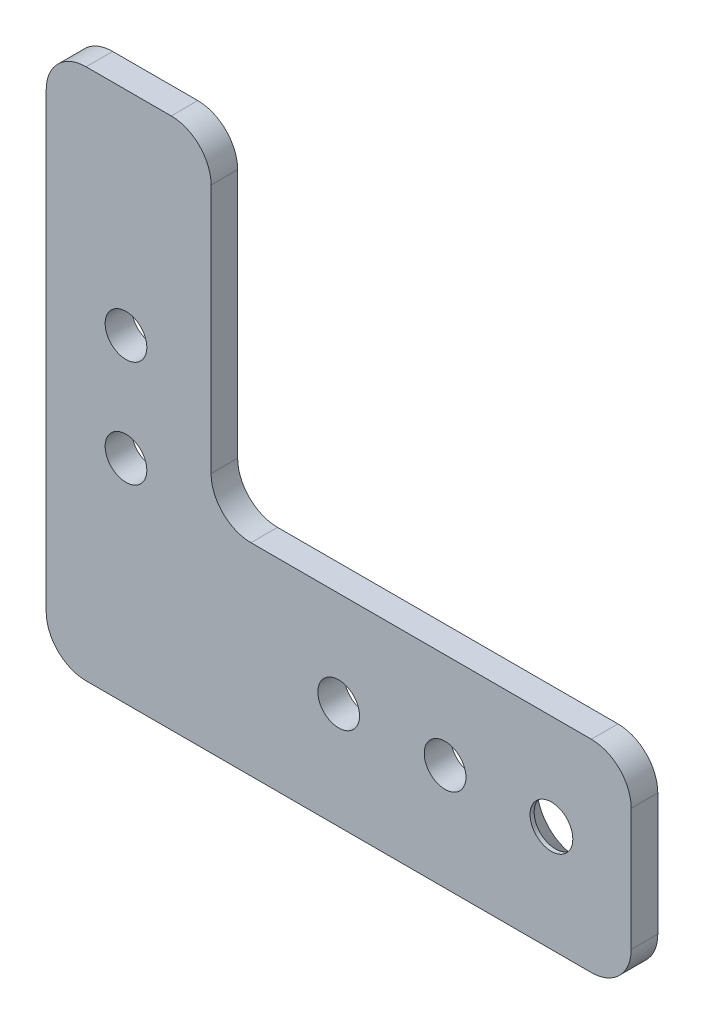
SolidWorks part; units mm, degrees
material "6061-T6 (SS)"
ref_plane "Front Plane" through (0, 0, 0) normal (0, 0, 1) x (1, 0, 0)
ref_plane "Top Plane" through (0, 0, 0) normal (0, 1, 0) x (1, 0, 0)
ref_plane "Right Plane" through (0, 0, 0) normal (1, 0, 0) x (0, 0, -1)
sketch "Sketch1" plane through (0, 0, 0) normal (0, 0, 1) x (1, 0, 0)
  line L0 (-15.24, 31.75) -> (-34.925, 31.75)
  line L1 (-34.925, -31.75) -> (34.925, -31.75) construction
  line L2 (-34.925, -31.75) -> (-34.925, 31.75)
  line L3 (-34.925, 31.75) -> (34.925, 31.75) construction
  line L4 (34.925, -31.75) -> (34.925, 31.75) construction
  line L5 (-34.925, -31.75) -> (34.925, 31.75) construction
  line L6 (-34.925, 31.75) -> (34.925, -31.75) construction
  line L7 (34.925, 31.75) -> (-15.24, 31.75) construction
  line L8 (34.925, 31.75) -> (34.925, -7.62) construction
  line L9 (34.925, -7.62) -> (-15.24, -7.62)
  line L10 (-15.24, 31.75) -> (-15.24, -7.62)
  line L19 (-25.4, 31.75) -> (-25.4, -31.75) construction
  line L20 (34.925, -7.62) -> (34.925, -31.75)
  line L24 (-34.925, -31.75) -> (34.925, -31.75)
  circle A0 centre (-25.4, -19.05) radius 2.4892
  circle A1 centre (-25.4, -6.35) radius 2.4892
  circle A2 centre (-25.4, 6.35) radius 2.4892
  circle A4 centre (0, -19.05) radius 2.4892
  circle A5 centre (12.7, -19.05) radius 2.4892
  circle A6 centre (25.4, -19.05) radius 2.4892
  point P0 (0, 0)
  dimension "D7" = 4.9784
  dimension "D1" = 69.85
  dimension "D2" = 63.5
  dimension "D3" = 24.13
  dimension "D4" = 19.685
  dimension "D5" = 9.525
  dimension "D6" = 34.925
  dimension "D9" = 12.7
  dimension "D10" = 12.7
  dimension "D11" = 12.7
  dimension "D13" = 12.7
  dimension "D15" = 12.7
base flange "Base-Flange1" sketch "Sketch1" thickness 3.175 reverse thickness direction no parameters "D1"=0.762
fillet "Fillet2" radius 4.7625 6 edges at (34.925, -31.75, -1.5875) (34.925, -7.62, -1.5875) (-15.24, -7.62, -1.5875) (-34.925, 31.75, -1.5875) (-34.925, -31.75, -1.5875) (-15.24, 31.75, -1.5875)
hole_wizard "CSK for #10 Flat Head Machine Screw1" positions "Sketch2" profile "Sketch3" countersink size "#10" standard "ANSI Inch"
sketch "Sketch2" plane through (0, 0, -3.175) normal (0, 0, -1) x (-1, 0, 0)
  point P0 (-25.4, -19.05)
  point P12 (0, 0)
  point P13 (0, -19.05)
  point P14 (0, 0)
  point P15 (-23.0546, -23.5031)
  point P16 (-25.4, -19.05)
  point P18 (0, 0)
sketch "Sketch3" plane through (25.4, -19.05, -3.175) normal (1, 0, 0) x (0, 1, 0)
  line L0 (0, 0) -> (0, 20.5838)
  line L1 (0, 20.5838) -> (2.5527, 19.05)
  line L2 (2.5527, 19.05) -> (2.5527, 2.6882)
  line L3 (2.5527, 2.6882) -> (4.8895, 0)
  line L5 (4.8895, 0) -> (0, 0)
  line L6 (-2.5527, 2.6882) -> (-4.8895, 0) construction
  line L10 (0, 20.5838) -> (-2.5527, 19.05) construction
  line L11 (0, -6.35) -> (0, 107.95) construction
  dimension "Hole Dia." = 5.1054
  dimension "Hole Depth" = 19.05
  dimension "Near C'Sink Dia." = 9.779
  dimension "Near C'Sink Angle" = 82
  dimension "Drill Angle" = 118
sketch "Bend-Lines1" [suppressed] plane through (0, 0, 0) normal (0, 1, 0) x (1, 0, 0)
sketch "Bounding-Box1" [suppressed] plane through (0, 0, 0) normal (0, 1, 0) x (1, 0, 0)
sheet metal parameters "Sheet-Metal3" thickness 3.175 parameters "D1"=0.762
flat pattern "Flat-Pattern3" [suppressed]
sketch "Bend-Lines2" plane through (0, 0, 0) normal (0, 1, 0) x (1, 0, 0)
sketch3d "Bounding-Box2" [suppressed]
  line L0 (-34.925, 31.75, 0) -> (34.925, 31.75, 0) construction
  line L1 (-34.925, -31.75, 0) -> (34.925, -31.75, 0) construction
  line L2 (-34.925, 31.75, 0) -> (-34.925, -31.75, 0) construction
  line L3 (34.925, 31.75, 0) -> (34.925, -31.75, 0) construction
sheet metal parameters "Sheet-Metal5" thickness 3.175 parameters "D1"=0.762
flat pattern "Flat-Pattern3"
sketch "Bend-Lines2" plane through (0, 0, 0) normal (0, 1, 0) x (1, 0, 0)
sketch3d "Bounding-Box2" [suppressed]
  line L0 (-34.925, 31.75, 0) -> (34.925, 31.75, 0) construction
  line L1 (-34.925, -31.75, 0) -> (34.925, -31.75, 0) construction
  line L2 (-34.925, 31.75, 0) -> (-34.925, -31.75, 0) construction
  line L3 (34.925, 31.75, 0) -> (34.925, -31.75, 0) construction
